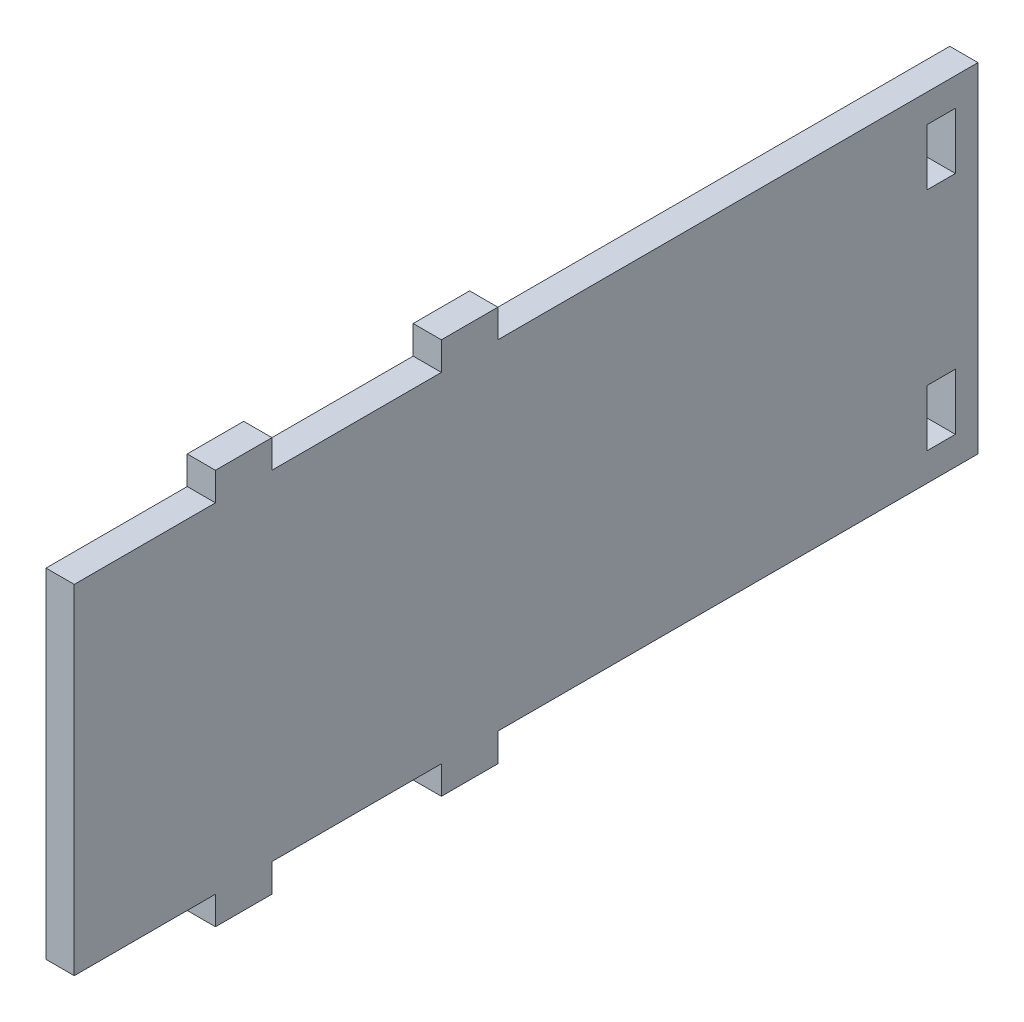
SolidWorks part; units mm, degrees
material "Maple"
ref_plane "Front" through (0, 0, 0) normal (0, 0, 1) x (1, 0, 0)
ref_plane "Top" through (0, 0, 0) normal (0, 1, 0) x (1, 0, 0)
ref_plane "Right" through (0, 0, 0) normal (1, 0, 0) x (0, 0, -1)
sketch "Sketch1" plane through (0, 0, 0) normal (1, 0, 0) x (0, 0, -1)
  line L0 (-70, 15) -> (70, 15) construction
  line L1 (-70, -17.5) -> (70, -17.5) construction
  line L2 (-70, -17.5) -> (-70, 17.5) construction
  line L3 (-70, 17.5) -> (70, 17.5) construction
  line L4 (70, -17.5) -> (70, 17.5) construction
  line L5 (-70, -17.5) -> (70, 17.5) construction
  line L6 (-70, 17.5) -> (70, -17.5) construction
  line L7 (0, 8.6195) -> (0, -6.7251) construction
  line L8 (-16.5735, 0) -> (15.6311, 0) construction
  line L9 (-10, -17.5) -> (-70, -17.5) construction
  line L10 (-57.5, 15) -> (-57.5, 17.5)
  line L11 (-70, -17.5) -> (-70, 15) construction
  line L12 (-67.5, 15) -> (-62.5, 15)
  line L13 (-67.5, 15) -> (-67.5, 17.5)
  line L14 (-67.5, 17.5) -> (-62.5, 17.5)
  line L15 (-62.5, 15) -> (-62.5, 17.5)
  line L16 (-67.5, 15) -> (-62.5, 17.5) construction
  line L17 (-67.5, 17.5) -> (-62.5, 15) construction
  line L18 (-57.5, 15) -> (-52.5, 15)
  line L19 (-52.5, 15) -> (-52.5, 17.5)
  line L20 (-57.5, 17.5) -> (-52.5, 17.5)
  line L21 (-47.5, 15) -> (-47.5, 17.5)
  line L22 (-47.5, 15) -> (-42.5, 15)
  line L23 (-42.5, 15) -> (-42.5, 17.5)
  line L24 (-47.5, 17.5) -> (-42.5, 17.5)
  line L25 (-37.5, 15) -> (-37.5, 17.5)
  line L26 (-37.5, 15) -> (-32.5, 15)
  line L27 (-32.5, 15) -> (-32.5, 17.5)
  line L28 (-37.5, 17.5) -> (-32.5, 17.5)
  line L29 (-27.5, 15) -> (-27.5, 17.5)
  line L30 (-27.5, 15) -> (-22.5, 15)
  line L31 (-22.5, 15) -> (-22.5, 17.5)
  line L32 (-27.5, 17.5) -> (-22.5, 17.5)
  line L33 (-27.5, -15) -> (-22.5, -15)
  line L34 (-22.5, -15) -> (-22.5, -17.5)
  line L35 (-27.5, -17.5) -> (-22.5, -17.5)
  line L36 (-27.5, -15) -> (-27.5, -17.5)
  line L37 (-37.5, -15) -> (-32.5, -15)
  line L38 (-32.5, -15) -> (-32.5, -17.5)
  line L39 (-37.5, -17.5) -> (-32.5, -17.5)
  line L40 (-37.5, -15) -> (-37.5, -17.5)
  line L41 (-47.5, -15) -> (-42.5, -15)
  line L42 (-42.5, -15) -> (-42.5, -17.5)
  line L43 (-47.5, -17.5) -> (-42.5, -17.5)
  line L44 (-47.5, -15) -> (-47.5, -17.5)
  line L45 (-57.5, -15) -> (-52.5, -15)
  line L46 (-52.5, -15) -> (-52.5, -17.5)
  line L47 (-57.5, -17.5) -> (-52.5, -17.5)
  line L48 (-57.5, -15) -> (-57.5, -17.5)
  line L49 (-67.5, -17.5) -> (-62.5, -17.5)
  line L50 (-62.5, -15) -> (-62.5, -17.5)
  line L51 (-67.5, -15) -> (-62.5, -15)
  line L52 (-67.5, -15) -> (-67.5, -17.5)
  line L53 (-70, 15) -> (-67.5, 15)
  line L54 (-62.5, 15) -> (-57.5, 15)
  line L55 (-52.5, 15) -> (-47.5, 15)
  line L56 (-42.5, 15) -> (-37.5, 15)
  line L57 (-32.5, 15) -> (-27.5, 15)
  line L58 (-22.5, 15) -> (-10, 15)
  line L59 (-10, 15) -> (-10, -17.5)
  line L61 (70, 15) -> (70, -17.5)
  line L62 (-10, 15) -> (-10, 17.5)
  line L63 (-10, 17.5) -> (-5, 17.5)
  line L64 (-5, 17.5) -> (-5, 15)
  line L65 (-5, 15) -> (10, 15)
  line L66 (10, 15) -> (10, 17.5)
  line L67 (10, 17.5) -> (15, 17.5)
  line L68 (15, 17.5) -> (15, 15)
  line L69 (15, 15) -> (30, 15)
  line L70 (30, 15) -> (30, 17.5)
  line L71 (30, 17.5) -> (35, 17.5)
  line L72 (35, 17.5) -> (35, 15)
  line L73 (35, 15) -> (50, 15)
  line L74 (50, 15) -> (50, 17.5)
  line L75 (50, 17.5) -> (55, 17.5)
  line L76 (55, 17.5) -> (55, 15)
  line L77 (55, 15) -> (70, 15)
  line L78 (-12, -7.5) -> (-12, -12.5)
  line L79 (-12, 12.5) -> (-14.5, 12.5)
  line L80 (-12, 12.5) -> (-12, 7.5)
  line L81 (-12, 7.5) -> (-14.5, 7.5)
  line L82 (-14.5, 12.5) -> (-14.5, 7.5)
  line L83 (-12, 12.5) -> (-14.5, 7.5) construction
  line L84 (-12, 7.5) -> (-14.5, 12.5) construction
  line L85 (-12, -7.5) -> (-14.5, -7.5)
  line L86 (-14.5, -7.5) -> (-14.5, -12.5)
  line L87 (-12, -12.5) -> (-14.5, -12.5)
  line L88 (-67.5, -15) -> (-70, -15)
  line L89 (-70, 15) -> (-90, 15)
  line L90 (-27.5, -17.5) -> (-32.5, -17.5)
  line L91 (-37.5, -17.5) -> (-42.5, -17.5)
  line L92 (-47.5, -17.5) -> (-52.5, -17.5)
  line L93 (-57.5, -17.5) -> (-62.5, -17.5)
  line L94 (-67.5, -15) -> (-70, -15)
  line L95 (-70, 15) -> (-70, -15)
  line L96 (-62.5, -15) -> (-57.5, -15)
  line L97 (-52.5, -15) -> (-47.5, -15)
  line L98 (-42.5, -15) -> (-37.5, -15)
  line L99 (-32.5, -15) -> (-27.5, -15)
  line L100 (-22.5, -15) -> (-10, -15)
  line L101 (-90, 15) -> (-90, -15)
  line L102 (-90, -15) -> (-70, -15)
  line L103 (-77.5, -17.5) -> (-72.5, -17.5)
  line L104 (-72.5, -15) -> (-72.5, -17.5)
  line L105 (-77.5, -15) -> (-72.5, -15)
  line L106 (-77.5, -15) -> (-77.5, -17.5)
  line L107 (-77.5, 15) -> (-77.5, 17.5)
  line L108 (-77.5, 15) -> (-72.5, 15)
  line L109 (-72.5, 15) -> (-72.5, 17.5)
  line L110 (-77.5, 17.5) -> (-72.5, 17.5)
  arc A0 (70, -17.5) -> (-10, -17.5) centre (30, -37) ccw
  point P0 (0, 0)
  point P15 (30, 7.5)
  point P20 (-65, 16.25)
  point P75 (-13.25, 10)
  dimension "D3" = 80
  dimension "D6" = 2.5
  dimension "D1" = 140
  dimension "D2" = 35
  dimension "D4" = 25
  dimension "D5" = 2.5
  dimension "D7" = 5
  dimension "D9" = 5
  dimension "D11" = 5
  dimension "D12" = 15
  dimension "D13" = 2
  dimension "D14" = 2.5
  dimension "D16" = 15
  dimension "D17" = 20
  dimension "D19" = 15
  dimension "D8" = 5
  dimension "D10" = 4
  dimension "D15" = 2
  dimension "D18" = 2
extrude "Boss-Extrude1" [suppressed] add sketch "Sketch1" along normal mid plane 2.5 contours L59 L58 L30 L57 L26 L56 L22 L55 L18 L54 L12 L53 L2 L9 L52 L51 L50 L48 L45 L46 L44 L41 L42 L40 L37 L38 L36 L33 L34 L82 L79 L80 L81 L78 L87 L86 L85 | A0 L61 L77 L76 L75 L74 L73 L72 L71 L70 L69 L68 L67 L66 L65 L64 L63 L62 L59 | L87 L78 L85 L86 | L79 L82 L81 L80 | L51 L52 L49 L50 | L41 L44 L43 L42 | L33 L36 L35 L34 | L32 L29 L30 L31 | L24 L21 L22 L23 | L12 L15 L14 L13
extrude "Boss-Extrude2" add sketch "Sketch1<3>" along normal blind 2.5 contours L33 L100 L59 L58 L30 L57 L26 L56 L22 L55 L18 L54 L12 L53 L95 L88 L51 L96 L45 L97 L41 L98 L37 L99 L78 L87 L86 L85 L82 L79 L80 L81 | L45 L48 L47 L46 | L20 L10 L18 L19 | L101 L102 L95 L89 | L110 L107 L89 L109 | L102 L106 L103 L104 region at (0, 16.25, 55) region at (0, 0, 40.3768) region at (0, 0, 80) region at (0, 16.25, 75) region at (0, -16.25, 75) region at (0, -16.25, 55)
sketch "Sketch1<3>" plane through (0, 0, 0) normal (1, 0, 0) x (0, 0, -1) same geometry as "Sketch1"
